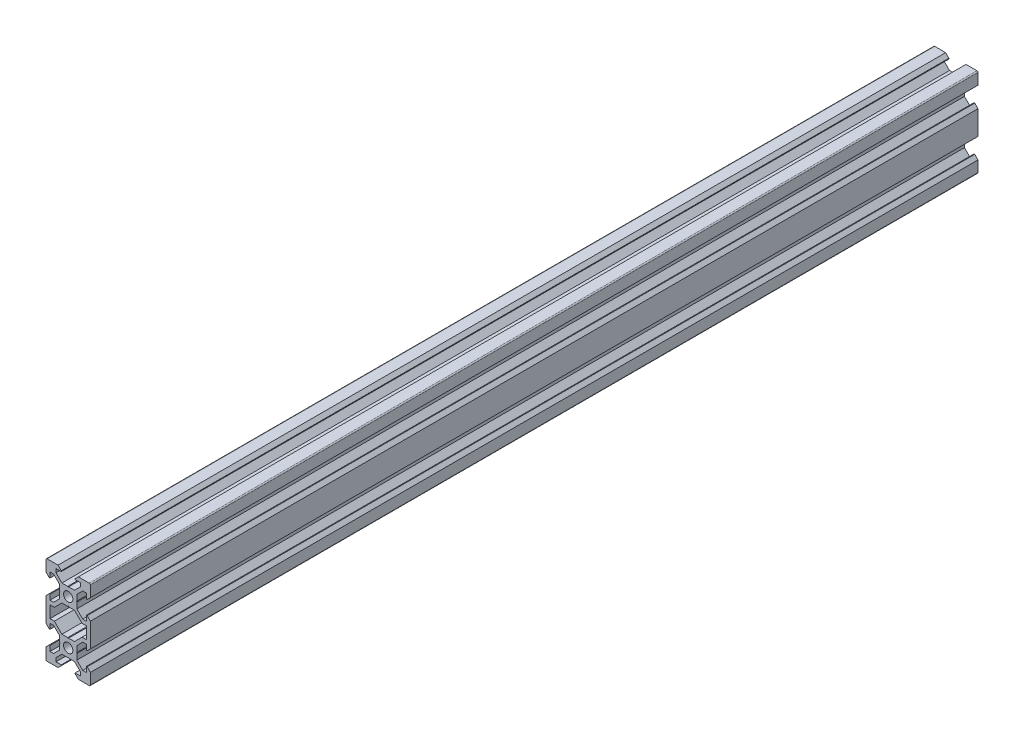
SolidWorks part; units mm, degrees
ref_plane "Plan de face" through (0, 0, 0) normal (0, 0, 1) x (1, 0, 0)
ref_plane "Plan de dessus" through (0, 0, 0) normal (0, 1, 0) x (1, 0, 0)
ref_plane "Plan de droite" through (0, 0, 0) normal (1, 0, 0) x (0, 0, -1)
ref_axis "Axe" through (0, 0, -13.782) along (0, 0, 1)
sketch "Esquisse1" plane through (0, 0, 0) normal (0, 0, 1) x (1, 0, 0)
  line L0 (0, 22.8977) -> (0, -22.8977) construction
  line L1 (-33.6074, 0) -> (33.6074, 0) construction
  line L2 (0, 0) -> (-22.2114, 22.2114) construction
  line L3 (-9.5, 10) -> (-4.58, 10)
  line L4 (-4.58, 10) -> (-3.125, 8.545)
  line L5 (-3.125, 8.545) -> (-3.125, 8.2)
  line L6 (-3.125, 8.2) -> (-5.5, 8.2)
  line L7 (-2.8393, 3.9) -> (-5.5, 6.5607)
  line L8 (-2.8393, 3.9) -> (-0.21, 3.9)
  line L9 (-5.5, 6.5607) -> (-5.5, 8.2)
  line L10 (0, 3.69) -> (0, 2.1)
  line L11 (-3.9, 2.8393) -> (-6.5607, 5.5)
  line L12 (-8.545, 3.125) -> (-8.2, 3.125)
  line L13 (-8.2, 3.125) -> (-8.2, 5.5)
  line L14 (-6.5607, 5.5) -> (-8.2, 5.5)
  line L15 (-10, 4.58) -> (-8.545, 3.125)
  line L16 (-10, 9.5) -> (-10, 4.58)
  line L17 (-0.21, 3.9) -> (0, 3.69)
  line L18 (-3.9, 2.8393) -> (-3.9, 0.21)
  line L20 (-3.9, 0.21) -> (-3.69, 0)
  line L21 (-0.21, -3.9) -> (0, -3.69)
  line L22 (0, -3.69) -> (0, -2.1)
  line L23 (-6.5607, -5.5) -> (-8.2, -5.5)
  line L24 (-2.8393, -3.9) -> (-0.21, -3.9)
  line L25 (-8.545, -3.125) -> (-8.2, -3.125)
  line L26 (-10, -4.58) -> (-8.545, -3.125)
  line L27 (-8.2, -3.125) -> (-8.2, -5.5)
  line L28 (-2.8393, -3.9) -> (-6.2393, -7.3)
  line L29 (-3.9, -2.8393) -> (-6.5607, -5.5)
  line L30 (-3.9, -2.8393) -> (-3.9, -0.21)
  line L31 (-3.9, -0.21) -> (-3.69, 0)
  line L32 (-6.2393, -7.3) -> (-8.2, -7.3)
  line L33 (-8.2, -7.3) -> (-8.2, -10)
  line L34 (-8.2, -10) -> (-10, -10)
  line L35 (-10, -10) -> (-10, -4.58)
  arc A0 (0, -2.1) -> (0, 2.1) centre (0, 0) cw
  arc A1 (-9.5, 10) -> (-10, 9.5) centre (-9.5, 9.5) ccw
  point P4 (0, 0)
  point P7 (0, 0)
  point P30 (-10, 10)
  dimension "D5" = 11
  dimension "D2" = 2.1
  dimension "D3" = 6.25
  dimension "D10" = 0.5
  dimension "D4" = 9.16
  dimension "D6" = 1.5
  dimension "D7" = 1.8
  dimension "D8" = 4.3
  dimension "D9" = 20
  dimension "D11" = 0.42
  dimension "D12" = 10
  dimension "D13" = 1.8
extrude "Boss.-Extru.1" add sketch "Esquisse1" along normal blind 400
sketch "Esquisse3" plane through (0, 0, 400) normal (0, 0, 1) x (1, 0, 0)
  line L0 (0, 0) -> (-9.8536, 9.8536) construction
  line L1 (-8.2, 8.2) -> (-8.2, 6.57)
  line L2 (-8.2, 6.57) -> (-7.54, 6.57)
  line L3 (-7.54, 6.57) -> (-6.57, 7.54)
  line L4 (-8.2, 3.125) -> (-8.2, 5.5) construction
  line L5 (-6.57, 8.2) -> (-6.57, 7.54)
  line L6 (-8.2, 8.2) -> (-6.57, 8.2)
  line L7 (-5.5, 6.5607) -> (-5.5, 8.2) construction
  arc A0 (-9.5, 10) -> (-10, 9.5) centre (-9.5, 9.5) ccw construction
  point P13 (-7.055, 7.055)
  point P14 (-6.57, 7.87)
  dimension "D1" = 1.07
extrude "Enlèv. mat.-Extru.1" [suppressed] cut sketch "Esquisse3" against normal through all
mirror "Symétrie1" about plane through (0, 3.69, 400) normal (-1, 0, 0) of "Enlèv. mat.-Extru.1", "Boss.-Extru.1"
mirror "Symétrie6" about plane through (-8.2, -10, 400) normal (0, 1, 0) of "Symétrie1", "Boss.-Extru.1"
